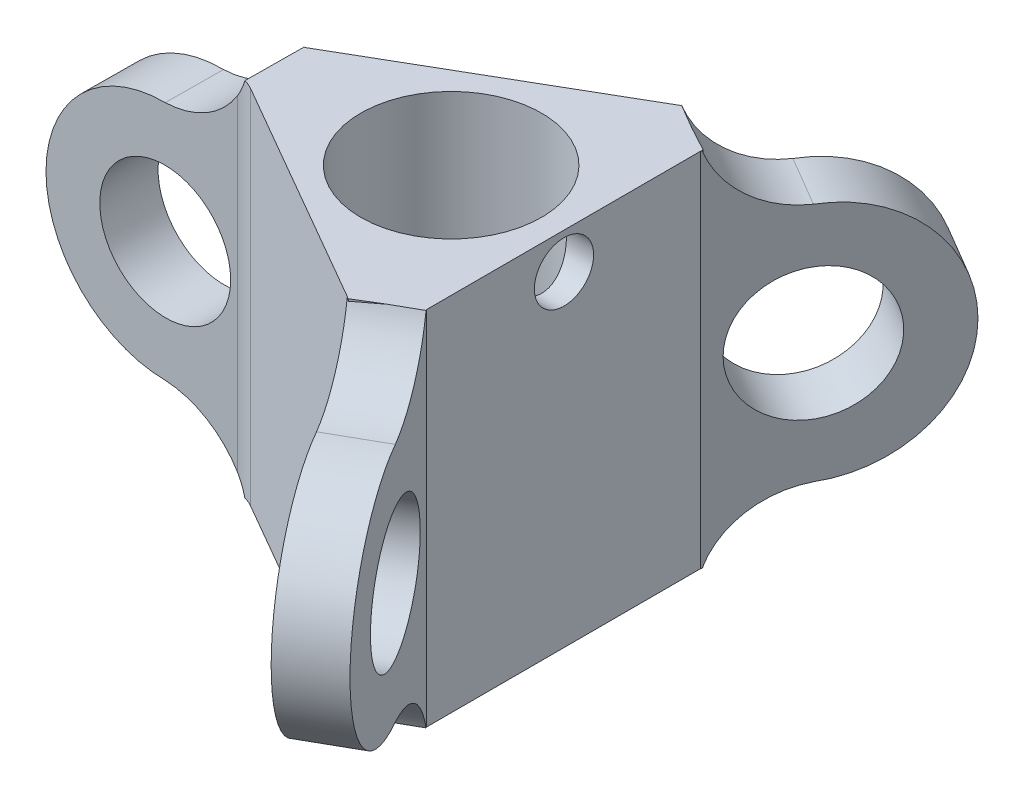
SolidWorks part; units mm, degrees
ref_plane "Front Plane" through (0, 0, 0) normal (0, 0, 1) x (1, 0, 0)
ref_plane "Top Plane" through (0, 0, 0) normal (0, 1, 0) x (1, 0, 0)
ref_plane "Right Plane" through (0, 0, 0) normal (1, 0, 0) x (0, 0, -1)
sketch "Sketch1" plane through (0, 0, 0) normal (0, 1, 0) x (1, 0, 0)
  line L8 (7.9066, 9.7927) -> (7.9176, -9.6734)
  line L9 (4.5082, -11.7326) -> (-12.3916, -1.9882)
  line L16 (0, 0) -> (4.3994, 11.6824) construction
  line L17 (-9.8213, 1.9945) -> (3.1477, 9.4919) construction
  line L23 (-12.3588, 1.9945) -> (4.3994, 11.6824)
  line L24 (-10.4569, 3.094) -> (2.5121, 10.5914) construction
  line L25 (-12.3588, 1.9945) -> (-12.3916, -1.9882)
  line L26 (4.5082, -11.7326) -> (7.9176, -9.6734)
  line L27 (7.9066, 9.7927) -> (4.3994, 11.6824)
  circle A14 centre (-0.075, 0) radius 6.35 construction
  point P22 (-0.0195, -0.0193)
  dimension "D1" = 1.27
  dimension "D4" = 3
  dimension "D5" = 12.4833
extrude "Boss-Extrude1" add sketch "Sketch1" along normal blind 25.4
sketch "Sketch3" plane through (0, 25.4, 0) normal (0, 1, 0) x (1, 0, 0)
  circle A0 centre (0, 0) radius 6.35
extrude "Cut-Extrude1" cut sketch "Sketch3" against normal blind 12.7
sketch "Sketch4" plane through (0, 0, 0) normal (0, -1, 0) x (1, 0, 0)
  circle A0 centre (0, 0) radius 3.556
extrude "Cut-Extrude2" cut sketch "Sketch4" against normal blind 12.7
sketch "Sketch10" plane through (-12.3744, 0, -0.1018) normal (-1, 0, -0.0082) x (-0.0082, 0, 1)
  line L0 (0.0987, 25.4) -> (0.0987, 0) construction
  line L1 (-1.8927, 25.4) -> (2.0901, 25.4) construction
  line L2 (-1.8927, 0) -> (2.0901, 0) construction
ref_plane "Plane2" through (-0.0008, 0, 0.0987) normal (-0.0082, 0, 1) x (1, 0, 0.0082)
sketch "Sketch11" plane through (-0.0008, 0, 0.0987) normal (-0.0082, 0, 1) x (1, 0, 0.0082)
  line L1 (-12.1517, 25.4) -> (-12.1517, 0)
  line L2 (-12.3748, 25.4) -> (4.6046, 25.4) construction
  line L3 (-12.3748, 0) -> (4.6046, 0) construction
  line L4 (-12.1517, 0) -> (-12.3748, 0)
  line L5 (-12.3748, 25.4) -> (-12.1517, 25.4)
  arc A0 (-18.0898, 21.1455) -> (-18.0898, 4.2545) centre (-18.0898, 12.7) ccw
  arc A1 (-12.3748, 25.4) -> (-18.0898, 21.1455) centre (-18.3712, 27.4893) cw
  arc A2 (-12.3748, 0) -> (-18.0898, 4.2545) centre (-18.3712, -2.0893) ccw
  circle A3 centre (-18.0898, 12.7) radius 4.6355
extrude "Boss-Extrude3" add sketch "Sketch11" along normal blind 2.032 and the other way blind 2.032
ref_axis "Axis1" through (0, 12.7, 0) along (0, 1, 0)
pattern_circular "CirPattern1" count 3 every 120 about axis through (0, 12.7, 0) along (0, 1, 0) of "Boss-Extrude3"
sketch "Sketch12" plane through (7.9121, 0, -0.0045) normal (1, 0, -0.0006) x (-0.0006, 0, -1)
  line L0 (-3.8951, 25.4) -> (3.9154, 25.4) construction
  line L1 (-3.8951, 25.4) -> (-3.8951, 0) construction
  line L2 (-3.8951, 0) -> (3.9154, 0) construction
  line L3 (3.9154, 25.4) -> (3.9154, 0) construction
  circle A0 centre (0.0101, 22.86) radius 2.0828
extrude "Cut-Extrude4" cut sketch "Sketch12" against normal blind 2.9718
fillet "Fillet3" radius 2.54 1 edges at (-12.3201, 12.7, 2.0294)
